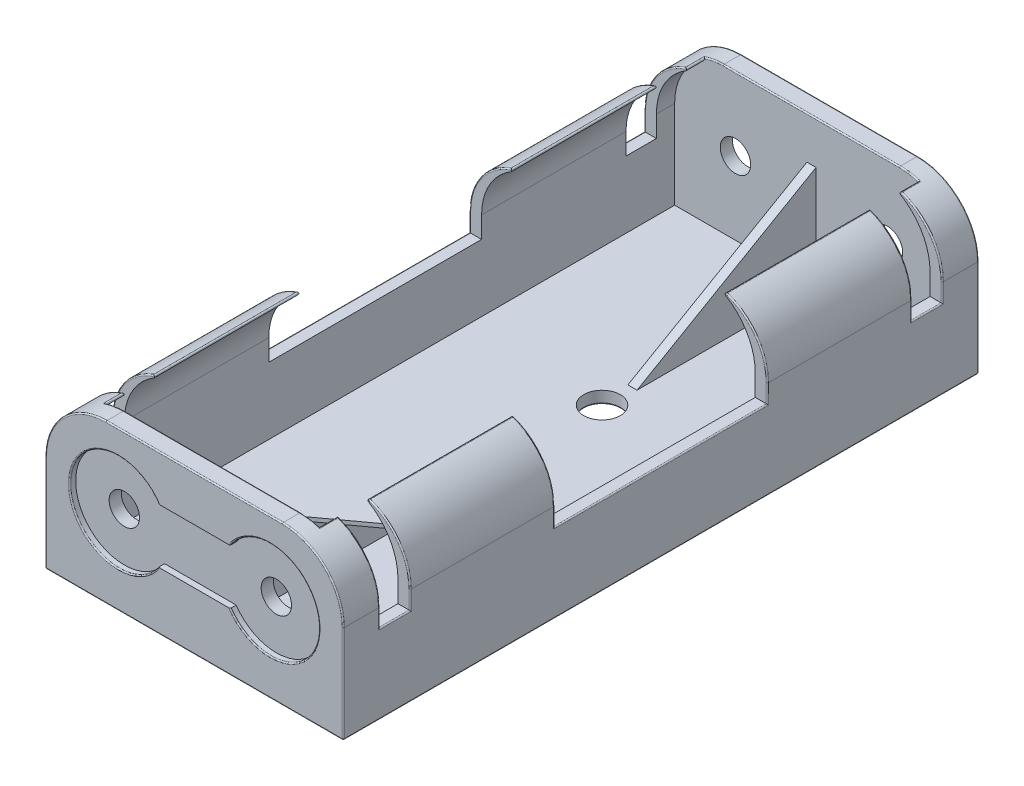
SolidWorks part; units mm, degrees
ref_plane "Front Plane" through (0, 0, 0) normal (0, 0, 1) x (1, 0, 0)
ref_plane "Top Plane" through (0, 0, 0) normal (0, 1, 0) x (1, 0, 0)
ref_plane "Right Plane" through (0, 0, 0) normal (1, 0, 0) x (0, 0, -1)
sketch "Sketch1" plane through (0, 0, 0) normal (0, 0, 1) x (1, 0, 0)
  line L0 (0, -6.5) -> (0, 6.5) construction
  line L1 (-12.25, -6.5) -> (12.25, -6.5)
  line L2 (-12.25, -6.5) -> (-12.25, 1.5)
  line L3 (-7.25, 6.5) -> (7.25, 6.5)
  line L4 (12.25, -6.5) -> (12.25, 1.5)
  line L5 (-12.25, -6.5) -> (12.25, 6.5) construction
  line L6 (-12.25, 6.5) -> (12.25, -6.5) construction
  arc A0 (-12.25, 1.5) -> (-7.25, 6.5) centre (-7.25, 1.5) cw
  arc A1 (7.25, 6.5) -> (12.25, 1.5) centre (7.25, 1.5) cw
  circle A2 centre (-6.25, 0.5) radius 1.25
  circle A3 centre (6.25, 0.5) radius 1.25
  point P0 (0, 0)
  dimension "D3" = 5
  dimension "D4" = 2.5
  dimension "D1" = 13
  dimension "D2" = 24.5
  dimension "D5" = 7
  dimension "D6" = 6.25
extrude "Boss-Extrude1" add sketch "Sketch1" along normal mid plane 52.25
sketch "Sketch2" plane through (0, 0, 26.125) normal (0, 0, 1) x (1, 0, 0)
  line L0 (11.25, 1.75) -> (11.25, -5.5)
  line L1 (11.25, -5.5) -> (-11.25, -5.5)
  line L2 (-11.25, -5.5) -> (-11.25, 1.75)
  line L3 (-12.25, -6.5) -> (12.25, -6.5) construction
  line L4 (-12.25, 1.5) -> (-12.25, -6.5) construction
  line L5 (12.25, -6.5) -> (12.25, 1.5) construction
  line L6 (6.25, 6.75) -> (-6.25, 6.75)
  arc A0 (11.25, 1.75) -> (6.25, 6.75) centre (6.25, 1.75) ccw
  arc A1 (-11.25, 1.75) -> (-6.25, 6.75) centre (-6.25, 1.75) cw
  point P12 (11.25, 6.75)
  point P15 (-11.25, 6.75)
  dimension "D6" = 5
  dimension "D7" = 5
  dimension "D1" = 1
  dimension "D2" = 1
  dimension "D3" = 1
  dimension "D4" = 12.25
  dimension "D5" = 12.25
extrude "Cut-Extrude1" cut sketch "Sketch2" against normal offset from surface (49.25 mm away) 1.5 from offset 1.5 contours L6 A1 L2 L1 L0 A0 up to face at (5, 0.5, -26.125) offset against normal yes
sketch "Sketch4" plane through (0, 0, 0) normal (1, 0, 0) x (0, 0, -1)
  line L0 (-26.125, -6.5) -> (26.125, -6.5) construction
  line L1 (-23.125, 0) -> (-20.625, 0)
  line L2 (-23.125, 0) -> (-23.125, 10)
  line L3 (-23.125, 10) -> (-20.625, 10)
  line L4 (-20.625, 0) -> (-20.625, 10)
  line L5 (-8.75, 0) -> (8.75, 0)
  line L6 (-8.75, 0) -> (-8.75, 10)
  line L7 (-8.75, 10) -> (8.75, 10)
  line L8 (8.75, 0) -> (8.75, 10)
  line L9 (20.625, 0) -> (23.125, 0)
  line L10 (20.625, 0) -> (20.625, 10)
  line L11 (20.625, 10) -> (23.125, 10)
  line L12 (23.125, 0) -> (23.125, 10)
  line L13 (-26.125, 6.5) -> (-26.125, 1.5) construction
  line L14 (26.125, 1.5) -> (26.125, 6.5) construction
  line L15 (0, -8.6474) -> (0, 13.5787) construction
  dimension "D1" = 2.5
  dimension "D2" = 10
  dimension "D3" = 6.5
  dimension "D4" = 3
  dimension "D5" = 17.5
  dimension "D6" = 3
extrude "Cut-Extrude2" cut sketch "Sketch4" along normal up to surface and the other way up to surface up to face at (12.25, -2.5, 0) other way up to face at (-12.25, -2.5, 0)
sketch "Sketch3" plane through (0, 0, 0) normal (1, 0, 0) x (0, 0, -1)
  line L0 (24.625, 3) -> (12.625, -3.9282)
  line L4 (24.625, -5.5) -> (24.625, 1.75) construction
  line L5 (24.625, 6.4499) -> (24.625, 1.75) construction
  line L6 (-26.125, -6.5) -> (26.125, -6.5) construction
  dimension "D1" = 60
  dimension "D3" = 9.5
rib "Rib2" sketch "Sketch3" sketch "Sketch3" thickness 0.75 extrusion direction parallel to sketch draft on no parameters "D1"=0.75
mirror "Mirror1" about plane through (0, 0, 0) normal (0, 0, 1) of "Rib2"
sketch "Sketch5" plane through (0, -5.5, 0) normal (0, 1, 0) x (1, 0, 0)
  line L0 (-0.375, 9.9026) -> (0.375, 9.9026) construction
  circle A0 centre (0, 7.4026) radius 1.5
  dimension "D1" = 3
  dimension "D2" = 2.5
extrude "Cut-Extrude3" cut sketch "Sketch5" against normal up to surface (1 mm away) up to face at (0, -6.5, 0)
mirror "Mirror2" about plane through (0, 0, 0) normal (0, 0, 1) of "Cut-Extrude3"
sketch "Sketch6" plane through (0, 0, 26.125) normal (0, 0, 1) x (1, 0, 0)
  circle A0 centre (6.25, 0.5) radius 4
  dimension "D1" = 8
extrude "Cut-Extrude4" cut sketch "Sketch6" against normal blind 0.5
mirror "Mirror3" about plane through (0, 0, 0) normal (0, 0, 1) of "Cut-Extrude4"
mirror "Mirror4" about plane through (0, 0, 0) normal (1, 0, 0) of "Mirror3", "Cut-Extrude4"
fillet "Fillet1" radius 0.1 64 edges at (0, 6.5, 24.625) (-7.9562, 6.4499, 23.875) (-7.604, 6.4875, 24.625) (-11.027, 4.7763, 23.125) (7.604, 6.4875, 24.625) (7.9562, 6.4499, 23.875) (11.027, 4.7763, 23.125) (0, -6.5, -5.9026) (0, -6.5, 8.9026) (0, -6.5, -26.125) (10.25, 0.5, -26.125) (-10.25, 0.5, -26.125) (-10.7855, 5.0355, -26.125) (-7.604, 6.4875, -24.625) (-7.9562, 6.4499, -23.875) (-11.027, 4.7763, -23.125) (7.9562, 6.4499, -23.875) (7.604, 6.4875, -24.625) (10.7855, 5.0355, -26.125) (11.027, 4.7763, -23.125) (0, 6.5, -26.125) (0, 6.5, -24.625) (7.9562, 6.4499, -14.6875) (11.027, 4.7763, -20.625) (11.027, 4.7763, -8.75) (11.027, 4.7763, 20.625) (7.9562, 6.4499, 14.6875) (11.027, 4.7763, 8.75) (-7.9562, 6.4499, 14.6875) (-11.027, 4.7763, 20.625) (-11.027, 4.7763, 8.75) (-11.027, 4.7763, -20.625) (-7.9562, 6.4499, -14.6875) (-11.027, 4.7763, -8.75) (-12.25, 0, 0) (-12.25, 0.75, 8.75) (-12.25, 0.75, 20.625) (-12.25, 0, 21.875) (-12.25, 0.75, 23.125) (-12.25, -6.5, 0) (-12.25, -2.5, -26.125) (-12.25, 0.75, -23.125) (-12.25, 0, -21.875) (-12.25, 0.75, -20.625) (-12.25, 0.75, -8.75) (-12.25, -2.5, 26.125) (-10.7855, 5.0355, 26.125) (0, 6.5, 26.125) (10.7855, 5.0355, 26.125) (0, -6.5, 26.125) (10.25, 0.5, 26.125) (-10.25, 0.5, 26.125) (12.25, 0.75, -20.625) (12.25, 0, -21.875) (12.25, 0.75, -23.125) (12.25, -2.5, -26.125) (12.25, -6.5, 0) (12.25, -2.5, 26.125) (12.25, 0.75, 23.125) (12.25, 0, 21.875) (12.25, 0.75, 20.625) (12.25, 0.75, 8.75) (12.25, 0, 0) (12.25, 0.75, -8.75)
sketch "Sketch7" plane through (0, 0, -26.125) normal (0, 0, -1) x (-1, 0, 0)
  line L0 (-6.25, 0.5) -> (6.25, 0.5) construction
  line L1 (-6.25, 2.75) -> (6.25, 2.75)
  line L2 (-6.25, -1.75) -> (6.25, -1.75)
  arc A0 (-6.25, 2.75) -> (-6.25, -1.75) centre (-6.25, 0.5) ccw
  arc A1 (6.25, -1.75) -> (6.25, 2.75) centre (6.25, 0.5) ccw
  point P4 (0, 0.5)
  dimension "D1" = 4.5
extrude "Cut-Extrude5" cut sketch "Sketch7" against normal blind 0.5
mirror "Mirror5" about plane through (0, 0, 0) normal (0, 0, 1) of "Cut-Extrude5"
